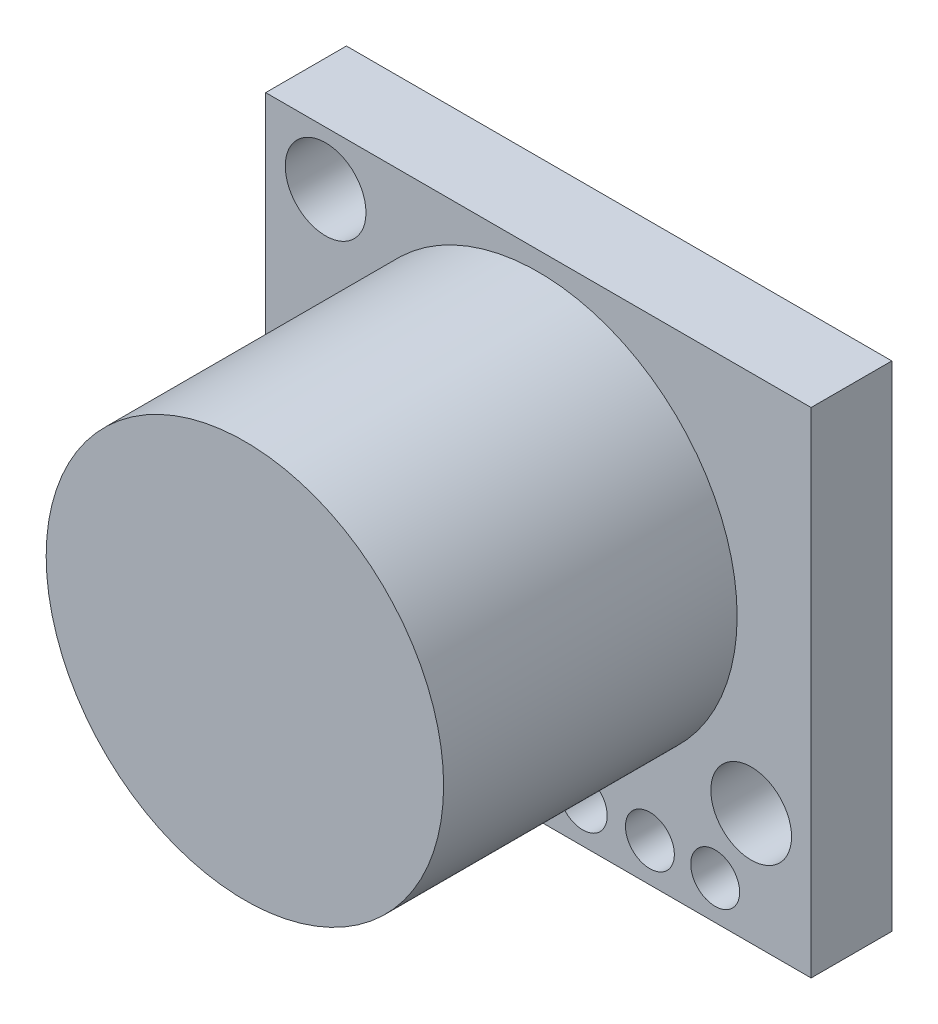
SolidWorks part; units mm, degrees
ref_plane "Front Plane" through (0, 0, 0) normal (0, 0, 1) x (1, 0, 0)
ref_plane "Top Plane" through (0, 0, 0) normal (0, 1, 0) x (1, 0, 0)
ref_plane "Right Plane" through (0, 0, 0) normal (1, 0, 0) x (0, 0, -1)
other "Center of Mass"
sketch "Sketch1" plane through (0, 0, 0) normal (0, 0, 1) x (1, 0, 0)
  line L1 (0, 0) -> (22.3, 0)
  line L2 (0, 0) -> (0, 20.2)
  line L3 (0, 20.2) -> (22.3, 20.2)
  line L4 (22.3, 0) -> (22.3, 20.2)
  circle A0 centre (2.45, 18) radius 1.65
  circle A1 centre (19.85, 4.6) radius 1.65
  dimension "D4" = 3.3
  dimension "D5" = 3.3
  dimension "D1" = 22.3
  dimension "D2" = 20.2
  dimension "D3" = 2.2
  dimension "D6" = 2.45
  dimension "D7" = 2.45
  dimension "D8" = 4.6
extrude "Boss-Extrude1" add sketch "Sketch1" along normal blind 3.3
sketch "Sketch2" plane through (0, 0, 3.3) normal (0, 0, 1) x (1, 0, 0)
  line L0 (19.85, 4.6) -> (2.45, 18) construction
  line L1 (4.3535, 1.5743) -> (17.3065, 1.5743) construction
  circle A0 centre (11.15, 11.3) radius 8.125
  circle A3 centre (4.3535, 1.5743) radius 1
  circle A6 centre (7.3803, 1.5743) radius 1
  circle A7 centre (12.9638, 1.5743) radius 1
  circle A8 centre (10.2378, 1.5743) radius 1
  circle A9 centre (15.7086, 1.5743) radius 1
  circle A10 centre (18.3781, 1.5743) radius 1
  dimension "D1" = 16.25
extrude "Boss-Extrude2" add sketch "Sketch2" along normal blind 12 contours A0 region at (11.15, 11.3, 3.3)
extrude "Cut-Extrude1" cut sketch "Sketch2<3>" against normal blind 12 contours A3 | A6 | A8 | A7 | A9 | A10 region at (4.3535, 1.5743, 3.3) region at (7.3803, 1.5743, 3.3) region at (12.9638, 1.5743, 3.3) region at (10.2378, 1.5743, 3.3) region at (15.7086, 1.5743, 3.3) region at (18.3781, 1.5743, 3.3)
sketch "Sketch2<3>" plane through (0, 0, 3.3) normal (0, 0, 1) x (1, 0, 0) same geometry as "Sketch2"
